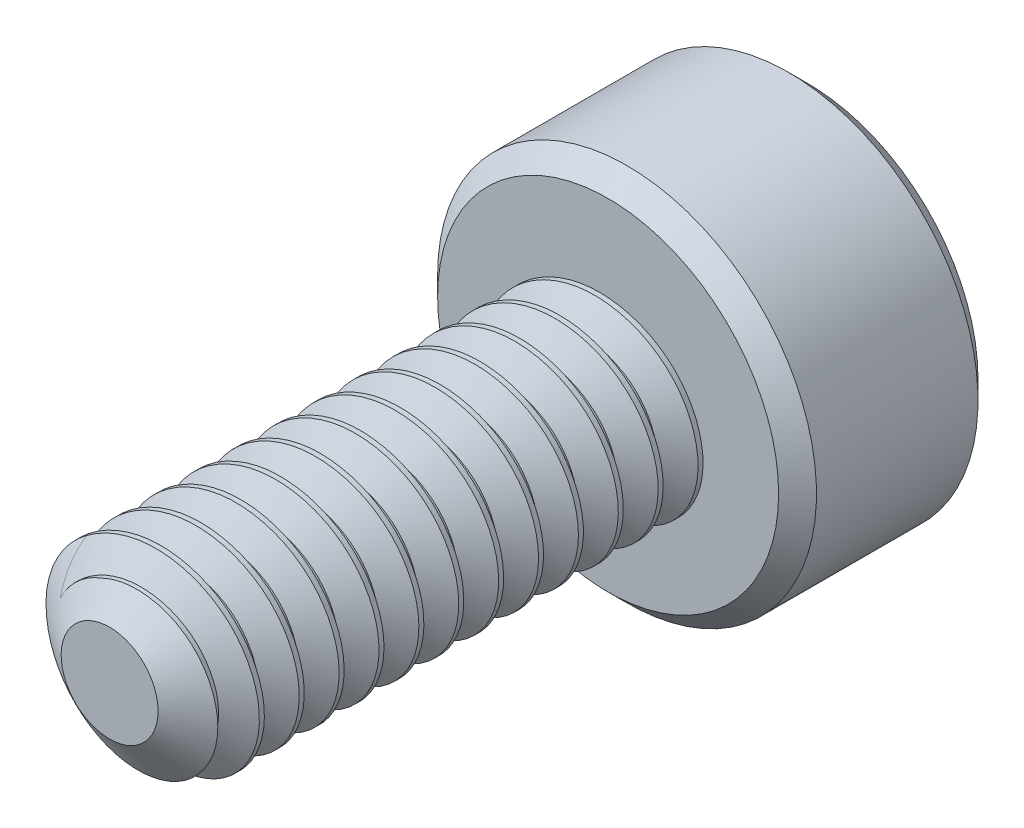
SolidWorks part; units mm, degrees
other "DetailItem1"
ref_plane "Front Plane" through (0, 0, 0) normal (0, 0, 1) x (1, 0, 0)
ref_plane "Top Plane" through (0, 0, 0) normal (0, 1, 0) x (1, 0, 0)
ref_plane "Right Plane" through (0, 0, 0) normal (1, 0, 0) x (0, 0, -1)
sketch "Sketch1" plane through (0, 0, 0) normal (0, 0, 1) x (1, 0, 0)
  circle A0 centre (0, 0) radius 1
  dimension "OD" = 2
extrude "Extrude1" add sketch "Sketch1" against normal blind 5
sketch "Sketch2" plane through (0, 0, 0) normal (0, 0, 1) x (1, 0, 0)
  circle A0 centre (0, 0) radius 1 construction
  circle A1 centre (0, 0) radius 1
curve "Helix/Spiral1" pitch 0.4 height 5.4 radius 1 centre (0, 0, 0) axis (0, 0, -1) start towards (0, 1, 0) parameters "pitch"=0.4
sketch "Sketch3" plane through (0, 0, 0) normal (1, 0, 0) x (0, 0, -1)
  line L0 (-0.35, 1) -> (-0.2, 0.7402)
  line L1 (-0.2, 0.7402) -> (-0.15, 0.7402)
  line L2 (-0.15, 0.7402) -> (0, 1)
  line L3 (-0.35, 1) -> (0, 1)
  line L4 (-0.175, 1) -> (-0.175, 0.7402) construction
  line L5 (-0.275, 0.8701) -> (-0.075, 0.8701) construction
  line L6 (0, 1) -> (0, -1) construction
  dimension "D1" = 0.05
  dimension "D2" = 0.2
  dimension "D3" = 60
sweep "Cut-Sweep1" cut profiles "Sketch3" path "Helix/Spiral1" align with end faces yes
sketch "Sketch4" plane through (0, 0, 0) normal (1, 0, 0) x (0, 0, -1)
  line L0 (0.3598, 1) -> (0, 0.4862)
  line L1 (0, 0.4862) -> (0, 1)
  line L2 (0.3598, 1) -> (0, 1)
  line L3 (-0.35, 1) -> (0, 1) construction
  line L4 (0, 0) -> (7.0209, 0) construction
  dimension "D1" = 55
  dimension "D2" = 0.254
revolve "Cut-Revolve1" cut sketch "Sketch4" angle 360 about L4
sketch "Sketch6" plane through (0, 0, -5) normal (0, 0, -1) x (-1, 0, 0)
  circle A0 centre (0, 0) radius 1.9
  dimension "head dia" = 3.8
extrude "Extrude2" add sketch "Sketch6" along normal blind 2
sketch "Sketch7" plane through (0, 0, -7) normal (0, 0, -1) x (-1, 0, 0)
  line L1 (0, 0.866) -> (-0.75, 0.433)
  line L2 (-0.75, 0.433) -> (-0.75, -0.433)
  line L3 (-0.75, -0.433) -> (0, -0.866)
  line L4 (0, -0.866) -> (0.75, -0.433)
  line L5 (0.75, -0.433) -> (0.75, 0.433)
  line L6 (0.75, 0.433) -> (0, 0.866)
  circle A0 centre (0, 0) radius 0.75 construction
  dimension "hex dia" = 1.5
extrude "Cut-Extrude1" cut sketch "Sketch7" against normal blind 1.125
sketch "Sketch8" plane through (0, 0, -7) normal (0, 0, -1) x (-1, 0, 0)
  circle A0 centre (0, 0) radius 0.866
extrude "Cut-Extrude2" cut sketch "Sketch8" against normal through all draft 45
chamfer "Chamfer1" distance 0.19 angle 45 2 edges at (-1.9, 0, -7) (-1.9, 0, -5)
sketch "Sketch10" plane through (0, 0, -5) normal (0, 0, 1) x (1, 0, 0)
  circle A1 centre (0, 0) radius 1
  circle A2 centre (0, 0) radius 1
  dimension "D1" = 0
ref_plane "Plane1" through (0, 0, 0) normal (0, 0, 1) x (1, 0, 0)
extrude "partial thread" [suppressed] add sketch "Sketch10" along normal up to surface (2 mm away) separate body up to plane "Plane1"
chamfer "Chamfer2" [suppressed] distance 0.04 angle 45
combine bodies "Combine1" [suppressed] operation type add bodies to combine 107 108
sketch "Sketch9" plane through (0, 0, 0) normal (1, 0, 0) x (0, 0, -1)
  line L0 (0, 1) -> (0, -1) construction
  line L1 (1, 1) -> (1, -1) construction
equation "\"D3@Helix/Spiral1\" = \"screw length@Extrude1\"+\"pitch@Helix/Spiral1\""
equation "\"D1@Sketch3\" = \"pitch@Helix/Spiral1\"*.125"
equation "\"D2@Sketch3\" = \"pitch@Helix/Spiral1\"*.5"
equation "\"D1@Cut-Extrude1\" = \"hex dia@Sketch7\"*.75"
equation "\"D1@Chamfer1\" = \"head dia@Sketch6\"*.05"
equation "\"D1@Sketch9\" = \"pitch@Helix/Spiral1\"*2.5"
equation "\"D1@Chamfer2\"=\"OD@Sketch1\"*.02"
